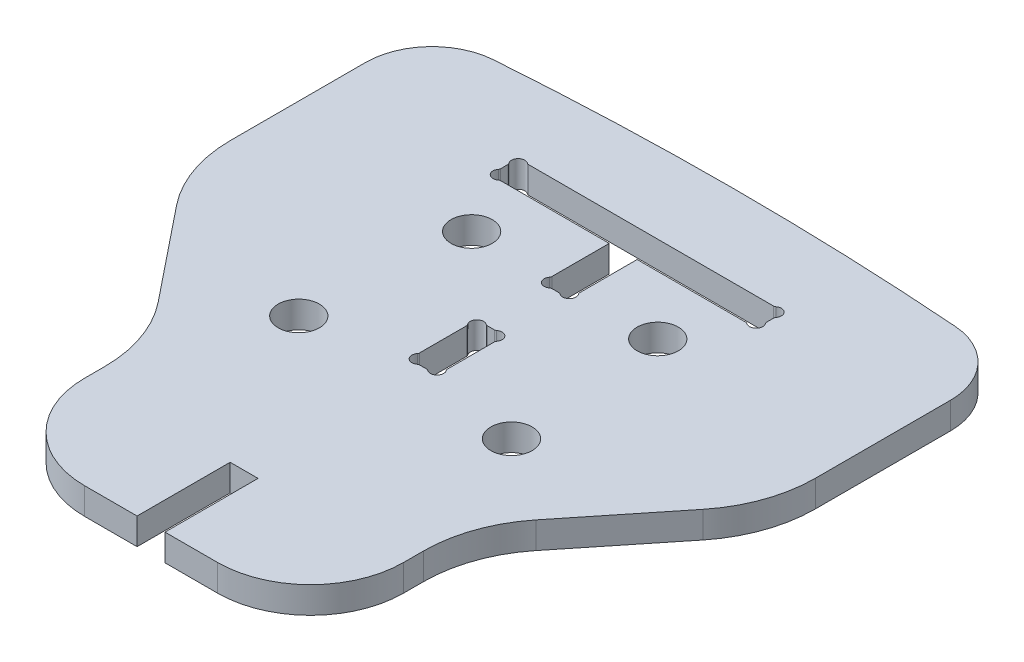
SolidWorks part; units mm, degrees
note: The reader was unsure of these and kept them because the rebuilt part matched: shared geometry of "草图5<3>".
material "自定义塑料碳纤维-1.6"
ref_plane "前视基准面" through (0, 0, 0) normal (0, 0, 1) x (1, 0, 0)
ref_plane "上视基准面" through (0, 0, 0) normal (0, 1, 0) x (1, 0, 0)
ref_plane "右视基准面" through (0, 0, 0) normal (1, 0, 0) x (0, 0, -1)
other "Configuration Table"
sketch "草图1" plane through (0, 0, 0) normal (0, 1, 0) x (1, 0, 0)
  line L0 (0, 0) -> (0, 106.8)
  line L1 (0, 106.8) -> (0, 341.8)
  line L2 (17, 341.1843) -> (17, 0)
  line L3 (17, 0) -> (0, 0)
  line L4 (-17, 341.1843) -> (-17, 0)
  line L5 (-17, 0) -> (0, 0)
  line L6 (0, 312.5) -> (22, 322.5)
  line L7 (22, 322.5) -> (22, 340.7679)
  line L8 (0, 312.5) -> (-22, 322.5)
  line L9 (-22, 322.5) -> (-22, 340.7679)
  line L10 (22, 322.5) -> (-22, 322.5)
  circle A0 centre (0, 0) radius 312.5
  circle A1 centre (0, 106.8) radius 235
  dimension "D1" = 625
  dimension "D3" = 470
  dimension "D2" = 106.8
  dimension "D4" = 17
  dimension "D5" = 17
  dimension "D6" = 5
  dimension "D7" = 5
  dimension "D8" = 10
extrude "凸台-拉伸1" add sketch "草图1" along normal blind 2 contours L2 A1 L1 A0 | L1 A1 L4 A0 | L2 L10 L1 L6 | L1 L10 L4 L8 | A0 L8 L4 | L4 L10 L8 | L4 A1 L9 L10 | L7 A1 L2 L10 | L6 L10 L2 | A0 L2 L6
sketch "草图2" plane through (0, 2, 0) normal (0, 1, 0) x (1, 0, 0)
  line L0 (0, 312.5) -> (0, 341.8) construction
  line L1 (-1.05, 318.5) -> (1.05, 318.5)
  line L2 (1.05, 318.5) -> (1.05, 323.6)
  line L3 (1.05, 323.6) -> (-1.05, 323.6)
  line L4 (0, 323.6) -> (0, 328.45)
  line L5 (-1.05, 328.45) -> (1.05, 328.45)
  line L6 (1.05, 328.45) -> (1.05, 333.55)
  line L7 (1.05, 333.55) -> (10, 333.55)
  line L8 (10, 333.55) -> (10, 335.65)
  line L9 (10, 335.65) -> (-10, 335.65)
  line L10 (-1.05, 318.5) -> (-1.05, 323.6)
  line L11 (-1.05, 328.45) -> (-1.05, 333.55)
  line L12 (-1.05, 333.55) -> (-10, 333.55)
  line L13 (-10, 333.55) -> (-10, 335.65)
  arc A0 (17, 312.0373) -> (-17, 312.0373) centre (0, 0) ccw construction
  arc A1 (22, 340.7679) -> (-22, 340.7679) centre (0, 106.8) ccw construction
  point P21 (0, 318.5)
  point P26 (0, 335.65)
  dimension "D6" = 318.5
  dimension "D1" = 2.1
  dimension "D2" = 10
  dimension "D3" = 5.1
  dimension "D4" = 5.1
  dimension "D5" = 4.85
  dimension "D7" = 1.05
extrude "切除-拉伸1" cut sketch "草图2" against normal through all contours L0 L5 L6 L7 L8 L9 | L5 L0 L9 L13 L12 L11 | L0 L1 L2 L3 | L1 L0 L3 L10
sketch "草图3" plane through (0, 2, 0) normal (0, 1, 0) x (1, 0, 0)
  line L0 (10, 334.9429) -> (9.2929, 335.65)
  line L1 (10, 333.55) -> (10, 335.65) construction
  line L2 (10, 335.65) -> (-10, 335.65) construction
  line L3 (10, 334.2571) -> (9.2929, 333.55)
  line L4 (1.05, 333.55) -> (10, 333.55) construction
  line L5 (1.05, 329.1571) -> (0.3429, 328.45)
  line L6 (-1.05, 328.45) -> (1.05, 328.45) construction
  line L7 (1.05, 328.45) -> (1.05, 333.55) construction
  line L8 (0.3429, 323.6) -> (1.05, 322.8929)
  line L9 (1.05, 318.5) -> (1.05, 323.6) construction
  line L10 (1.05, 319.2071) -> (0.3429, 318.5)
  line L11 (-1.05, 318.5) -> (1.05, 318.5) construction
  line L12 (0.6964, 323.2464) -> (1.05, 323.6)
  line L13 (0.6964, 318.8536) -> (1.05, 318.5)
  line L14 (1.05, 323.6) -> (-1.05, 323.6) construction
  line L15 (0.6964, 328.8036) -> (1.05, 328.45)
  line L16 (9.6464, 333.9036) -> (10, 333.55)
  line L17 (9.6464, 335.2964) -> (10, 335.65)
  circle A0 centre (9.6464, 333.9036) radius 0.5
  circle A1 centre (9.6464, 335.2964) radius 0.5
  circle A2 centre (0.6964, 328.8036) radius 0.5
  circle A3 centre (0.6964, 323.2464) radius 0.5
  circle A4 centre (0.6964, 318.8536) radius 0.5
  line M11 (-10, 335.65) -> (10, 335.65)
  line M12 (10, 335.65) -> (10, 333.55)
  line M13 (10, 333.55) -> (1.05, 333.55)
  line M14 (1.05, 333.55) -> (1.05, 328.45)
  line M15 (1.05, 328.45) -> (-1.05, 328.45)
  line M19 (-1.05, 323.6) -> (1.05, 323.6)
  line M20 (1.05, 323.6) -> (1.05, 318.5)
  line M21 (1.05, 318.5) -> (-1.05, 318.5)
  dimension "D1" = 1
extrude "切除-拉伸2" cut sketch "草图3" against normal through all contours A1 M12 | A1 M11 | A0 M12 | A0 M13 | A2 M14 | A2 M15 | A3 M20 | A3 M19 | A4 M20 | A4 M21
mirror "镜向1" about plane through (0, 0, 0) normal (1, 0, 0) of "切除-拉伸2"
fillet "圆角1" radius 0.2 20 edges at (1.05, 1, -322.8929) (1.05, 1, -319.2071) (-0.3429, 1, -318.5) (0.3429, 1, -318.5) (-1.05, 1, -319.2071) (-1.05, 1, -322.8929) (-0.3429, 1, -323.6) (0.3429, 1, -323.6) (-1.05, 1, -329.1571) (-0.3429, 1, -328.45) (0.3429, 1, -328.45) (1.05, 1, -329.1571) (9.2929, 1, -335.65) (10, 1, -334.9429) (10, 1, -334.2571) (9.2929, 1, -333.55) (-9.2929, 1, -333.55) (-10, 1, -334.2571) (-10, 1, -334.9429) (-9.2929, 1, -335.65)
sketch "草图4" plane through (0, 2, 0) normal (0, 1, 0) x (1, 0, 0)
  line L0 (0, 312.5) -> (0, 341.8)
  line L1 (9.218, 335.65) -> (-9.218, 335.65) construction
  arc A0 (17, 312.0373) -> (-17, 312.0373) centre (0, 0) ccw construction
  arc A1 (22, 340.7679) -> (-22, 340.7679) centre (0, 106.8) ccw construction
  circle A2 centre (7, 329.15) radius 1.55
  circle A3 centre (8, 317.15) radius 1.55
  dimension "D5" = 3.1
  dimension "D1" = 7
  dimension "D2" = 6.5
  dimension "D3" = 8
  dimension "D4" = 12
extrude "切除-拉伸3" cut sketch "草图4" against normal through all contours A2 | A3
mirror "镜向2" about plane through (0, 0, 0) normal (1, 0, 0) of "切除-拉伸3"
fillet "圆角2" radius 5 2 edges at (22, 1, -340.7679) (-22, 1, -340.7679)
sketch "草图5" plane through (0, 2, 0) normal (0, 1, 0) x (1, 0, 0)
  line L0 (-17, 312.0373) -> (-17, 298.0373)
  line L1 (-17, 298.0373) -> (17, 298.0373)
  line L2 (17, 298.0373) -> (17, 312.0373)
  line L4 (-12, 310.0373) -> (-22, 322.5)
  line L5 (12, 310.0373) -> (22, 322.5)
  line L6 (12, 298.0373) -> (12, 310.0373)
  line L7 (12, 310.0373) -> (17, 310.0373)
  line L8 (-12, 298.0373) -> (-12, 310.0373)
  line L9 (-12, 310.0373) -> (-17, 310.0373)
  line L10 (22, 322.5) -> (12, 322.5)
  line L11 (12, 322.5) -> (12, 310.0373)
  line L12 (-22, 322.5) -> (-12, 322.5)
  line L13 (-12, 322.5) -> (-12, 310.0373)
  line L14 (-22, 322.5) -> (-22, 310.0373)
  line L15 (-22, 310.0373) -> (-17, 310.0373)
  line L16 (22, 322.5) -> (22, 310.0373)
  line L17 (22, 310.0373) -> (17, 310.0373)
  arc A1 (17, 312.0373) -> (-17, 312.0373) centre (0, 0) ccw construction
  arc A2 (17, 312.0373) -> (-17, 312.0373) centre (0, 0) ccw
  dimension "D1" = 14
  dimension "D2" = 5
  dimension "D3" = 5
  dimension "D4" = 12
extrude "凸台-拉伸2" add sketch "草图5" against normal up to surface (2 mm away) contours L2 A2 L0 L9 L8 L1 L6 L7 | L13 A2 L4 | L5 A2 L11 | A2 L13 L12 L4 | A2 L5 L10 L11
extrude "切除-拉伸5" cut sketch "草图5<3>" against normal blind 10 contours A2 L4 L14 L15 L0 | L4 A2 L0 L9 | A2 L2 L17 L16 L5 | L2 A2 L5 L7
sketch "草图5<3>" plane through (0, 2, 0) normal (0, 1, 0) x (1, 0, 0) same geometry as "草图5"
sketch "草图6" plane through (0, 2, 0) normal (0, 1, 0) x (1, 0, 0)
  line L0 (1.05, 298.0373) -> (1.05, 305.0373)
  line L2 (1.05, 305.0373) -> (-1.05, 305.0373)
  line L3 (-1.05, 305.0373) -> (-1.05, 298.0373)
  line L4 (-1.05, 298.0373) -> (1.05, 298.0373)
  line L8 (-12, 298.0373) -> (12, 298.0373) construction
  point P3 (0, 298.0373)
  dimension "D1" = 2.1
  dimension "D2" = 7
extrude "切除-拉伸4" cut sketch "草图6" against normal up to surface (2 mm away) up to face at (0, 0, -332.7114)
fillet "圆角8" radius 7 2 edges at (12, 1, -298.0373) (-12, 1, -298.0373)
fillet "圆角5" radius 10 2 edges at (22, 1, -322.5) (-22, 1, -322.5)
fillet "圆角6" radius 10 2 edges at (12, 1, -310.0373) (-12, 1, -310.0373)
